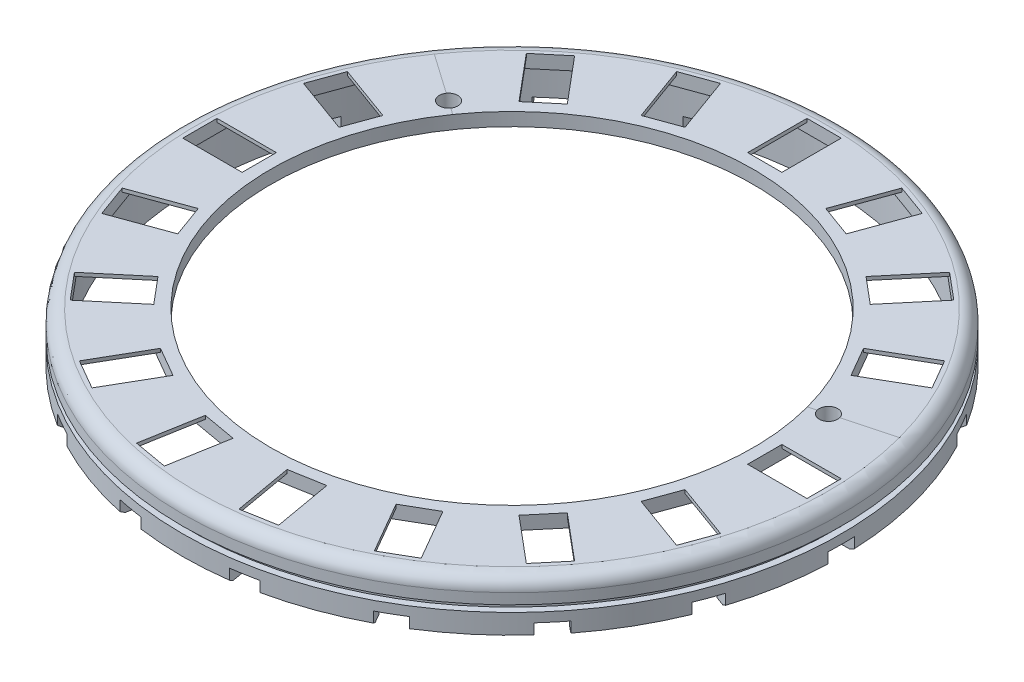
SolidWorks part; units mm, degrees
ref_plane "Front Plane" through (0, 0, 0) normal (0, 0, 1) x (1, 0, 0)
ref_plane "Top Plane" through (0, 0, 0) normal (0, 1, 0) x (1, 0, 0)
ref_plane "Right Plane" through (0, 0, 0) normal (1, 0, 0) x (0, 0, -1)
sketch "Sketch1" plane through (0, 0, 0) normal (0, 1, 0) x (1, 0, 0)
  circle A0 centre (0, 0) radius 25
  dimension "D1" = 50
extrude "Boss-Extrude1" add sketch "Sketch1" along normal blind 4
sketch "Sketch4" plane through (0, 4, 0) normal (0, 1, 0) x (1, 0, 0)
  circle A0 centre (0, 0) radius 18.3
  dimension "D1" = 36.6
extrude "Cut-Extrude2" cut sketch "Sketch4" against normal through all
sketch "Sketch5" plane through (0, 0, 0) normal (0, 0, 1) x (1, 0, 0)
  line L0 (0, 0) -> (0, 4) construction
  line L1 (18.3, 4) -> (-18.3, 4) construction
  line L2 (25, 0) -> (25, 4) construction
  line L3 (25, 2.2) -> (24.5, 2.2)
  line L4 (25, 2.2) -> (25, 1.7)
  line L5 (25, 1.7) -> (24.5, 1.7)
  line L6 (24.5, 2.2) -> (24.5, 1.7)
  line L8 (25, 4) -> (-25, 4) construction
  dimension "D1" = 1.8
  dimension "D2" = 0.5
  dimension "D3" = 49
revolve "Cut-Revolve1" cut sketch "Sketch5" angle 360 about L0
sketch "Sketch2" plane through (0, 0, 0) normal (0, 1, 0) x (1, 0, 0)
  circle A0 centre (0, 0) radius 23.9
  dimension "D1" = 47.8
extrude "Cut-Extrude1" cut sketch "Sketch2" along normal offset from surface (3 mm away) 1 up to face at (0, 4, 18.3)
sketch "Sketch6" plane through (0, 0, 0) normal (0, 0, 1) x (1, 0, 0)
  line L0 (0, 0) -> (0, 4) construction
  line L1 (18.3, 4) -> (-18.3, 4) construction
  line L2 (-25, 0.2021) -> (-24.65, 0)
  line L3 (-25, 1.7) -> (-25, 0) construction
  line L4 (-25, 0) -> (25, 0) construction
  line L5 (-25, 0.2021) -> (-25, 0)
  line L6 (-25, 0) -> (-24.65, 0)
  dimension "D1" = 49.3
  dimension "D2" = 30
revolve "Cut-Revolve2" cut sketch "Sketch6" angle 360 about L0
sketch "Sketch7" plane through (0, 4, 0) normal (0, 1, 0) x (1, 0, 0)
  line L0 (0, 0) -> (25, 0) construction
  line L1 (0, 0) -> (0, 9.991) construction
  line L2 (19.175, 1.3) -> (23.675, 1.3)
  line L3 (23.675, 1.3) -> (23.675, -1.3)
  line L4 (19.175, -1.3) -> (23.675, -1.3)
  line L5 (19.175, 1.3) -> (19.175, -1.3)
  circle A0 centre (0, 0) radius 25 construction
  point P8 (19.175, 0)
  point P14 (0, 0)
  point P15 (22.6405, 6.9219)
  dimension "D2" = 4.5
  dimension "D1" = 47.35
  dimension "D3" = 2.6
extrude "Cut-Extrude4" cut sketch "Sketch7" against normal up to next
sketch "Sketch14" plane through (23.675, 0, 0) normal (1, 0, 0) x (0, 0, -1)
  line L0 (0, 0) -> (0, 1.6878) construction
  line L1 (-1, 1) -> (1, 1)
  line L2 (-1, 1) -> (-1, 0)
  line L3 (-1, 0) -> (1, 0)
  line L4 (1, 1) -> (1, 0)
  line L5 (0, 1.7) -> (0, 0.2021) construction
  line L6 (-24.65, 0) -> (24.65, 0) construction
  line L7 (25, 4) -> (-25, 4) construction
  dimension "D1" = 2
  dimension "D2" = 3
extrude "Cut-Extrude9" cut sketch "Sketch14" along normal up to next
pattern_circular "CirPattern3" count 11 every 20 about axis through (0, 4, 0) along (0, -1, 0) of "Cut-Extrude4", "Cut-Extrude9"
sketch "Sketch9" plane through (0, 4, 0) normal (0, 1, 0) x (1, 0, 0)
  line L0 (0, 0) -> (25, 0) construction
  line L1 (0, 0) -> (21.6506, 12.5) construction
  line L2 (19.8532, 12.9633) -> (21.1532, 10.7117)
  line L3 (15.956, 10.7133) -> (19.8532, 12.9633)
  line L4 (17.256, 8.4617) -> (21.1532, 10.7117)
  line L5 (-0.65, 1.1258) -> (21.0006, 13.6258) construction
  line L6 (15.956, 10.7133) -> (17.256, 8.4617)
  circle A1 centre (0, 0) radius 25 construction
  point P14 (0.65, -1.1258)
  point P16 (22.3006, 11.3742)
  dimension "D1" = 30
  dimension "D2" = 2.6
  dimension "D3" = 23.675
  dimension "D4" = 4.5
extrude "Cut-Extrude5" cut sketch "Sketch9" against normal up to next
sketch "Sketch15" plane through (20.5032, 0, -11.8375) normal (-0.866, 0, 0.5) x (0.5, 0, 0.866)
  line L0 (0, 0) -> (0, 4) construction
  line L1 (1.3, 4) -> (-1.3, 4) construction
  line L2 (25, 4) -> (-25, 4) construction
  line L3 (-1, 1) -> (1, 1)
  line L4 (-1, 1) -> (-1, 0)
  line L5 (-1, 0) -> (1, 0)
  line L6 (1, 1) -> (1, 0)
  dimension "D1" = 3
  dimension "D2" = 2
extrude "Cut-Extrude10" cut sketch "Sketch15" against normal up to next
sketch "Sketch16" plane through (16.606, 0, -9.5875) normal (0.866, 0, -0.5) x (-0.5, 0, -0.866)
  line L0 (0, 0) -> (0, 4.7339) construction
  line L1 (-3.1617, 0) -> (3.1617, 0) construction
  line L2 (0, 0.2021) -> (0, 0) construction
  line L3 (-1, 1) -> (1, 1) construction
  line L4 (-18.3, 3) -> (18.3, 3) construction
  line L5 (-2.3664, 3) -> (2.3664, 3)
  arc A0 (-2.3664, 3) -> (2.3664, 3) centre (0, 0.7) cw
  dimension "D1" = 3.3
  dimension "D2" = 0.3
extrude "Cut-Extrude11" cut sketch "Sketch16" along normal up to surface (4.5 mm away) up to face at (20.5032, 3.5, -11.8375)
pattern_circular "CirPattern4" count 6 every 20 about axis through (0, 4, 0) along (0, -1, 0) of "Cut-Extrude5", "Cut-Extrude10", "Cut-Extrude11" reverse direction yes
sketch "Sketch3" plane through (0, 0, 0) normal (0, 0, 1) x (1, 0, 0)
  line L0 (-23.9, 3) -> (-18.3, 3)
  line L1 (18.4, 3) -> (18.975, 3.7332)
  line L2 (-23.9, 3) -> (23.9, 3) construction
  line L3 (18.975, 3.7332) -> (23.775, 3.7332)
  line L4 (23.775, 3.7332) -> (23.9, 3)
  line L7 (18.4, 3) -> (23.9, 3)
  line L12 (23.675, 3) -> (23.675, 4) construction
  line L15 (17.256, 3.7332) -> (21.1532, 3.7332) construction
  line L16 (19.175, 3) -> (19.175, 4) construction
  line L17 (-18.3, 3) -> (18.3, 3) construction
  line L18 (-18.3, 3) -> (18.3, 3) construction
  dimension "D1" = 0.1
  dimension "D2" = 0.1
  dimension "D3" = 0.2
ref_plane "Plane1" through (0, 0, -21.175) normal (0, 0, -1) x (-1, 0, 0)
extrude "Cut-Extrude12" [suppressed] cut sketch "Sketch3" against normal up to vertex and the other way up to vertex contours L3 L4 L7 L1 up to point (19.175, 4, -1.3) other way up to point (19.175, 4, 1.3)
pattern_circular "CirPattern10" [suppressed] count 11 every 20 of bodies 118
fillet "Fillet1" radius 1 1 edges at (0, 4, 25)
hole_wizard "Ø1.4 (1.4) Diameter Hole1" positions "Sketch19" profile "Sketch18" hole size "Ø1.4" standard "DIN" end condition up to next
sketch "Sketch19" plane through (0, 4, 0) normal (0, 1, 0) x (1, 0, 0)
  line L0 (0, 0) -> (18.3, 0) construction
  line L1 (0, 0) -> (18.9321, 5.0729) construction
  line L2 (0, 0) -> (-22.2472, 8.0973) construction
  line L3 (-21.8026, 9.3189) -> (-22.6918, 6.8757) construction
  line L4 (0, 0) -> (-16.0554, 11.2421) construction
  circle A0 centre (0, 0) radius 19.6 construction
  circle A1 centre (0, 0) radius 18.3 construction
  point P15 (18.9321, 5.0729)
  point P27 (-16.0554, 11.2421)
  dimension "D1" = 39.2
  dimension "D2" = 15
  dimension "D3" = 35
sketch "Sketch18" plane through (18.9321, 4, -5.0729) normal (1, 0, 0) x (0, 0, 1)
  line L0 (0, 0) -> (0, 1)
  line L1 (0, 1) -> (0.7, 1)
  line L2 (0.7, 1) -> (0.7, 0)
  line L5 (0.7, 0) -> (0, 0)
  line L11 (0, -6.35) -> (0, 107.95) construction
  dimension "Thru Hole Dia." = 1.4
  dimension "Thru Hole Depth" = 1
sketch "Sketch21" plane through (0, 4, 0) normal (0, 1, 0) x (1, 0, 0)
  line L0 (0, 0) -> (25, 0) construction
  line L1 (-14.9905, 10.4964) -> (-20.4788, 14.3394)
  line L2 (17.6764, 4.7364) -> (24.1481, 6.4705)
  line L3 (-14.9905, 10.4964) -> (0, 0) construction
  line L4 (0, 0) -> (17.6764, 4.7364) construction
  circle A0 centre (0, 0) radius 25 construction
  arc A1 (-20.4788, 14.3394) -> (24.1481, 6.4705) centre (0, 0) ccw
  circle A2 centre (0, 0) radius 18.3 construction
  arc A3 (-14.9905, 10.4964) -> (17.6764, 4.7364) centre (0, 0) ccw
  dimension "D1" = 35
  dimension "D2" = 15
wrap "Wrap2" sketch "Sketch21" wrap type scribe source sketch "Sketch21" face at (18.9321, 4, -4.3729)
sketch "Sketch23" plane through (19.175, 0, 0) normal (1, 0, 0) x (0, 0, -1)
  line L0 (0, 1) -> (0, 0.7) construction
  line L1 (-1, 1) -> (1, 1) construction
  line L2 (-18.3, 3) -> (18.3, 3) construction
  line L3 (-2.3664, 3) -> (2.3664, 3)
  arc A0 (2.3664, 3) -> (-2.3664, 3) centre (0, 0.7) ccw
  dimension "D1" = 6.6
  dimension "D2" = 0.3
extrude "Cut-Extrude13" cut sketch "Sketch23" along normal up to vertex (4.5 mm away) up to point (23.675, 4, -1.3)
pattern_circular "CirPattern14" count 11 every 20 about axis through (0, 4, 0) along (0, -1, 0) of "Cut-Extrude13"
